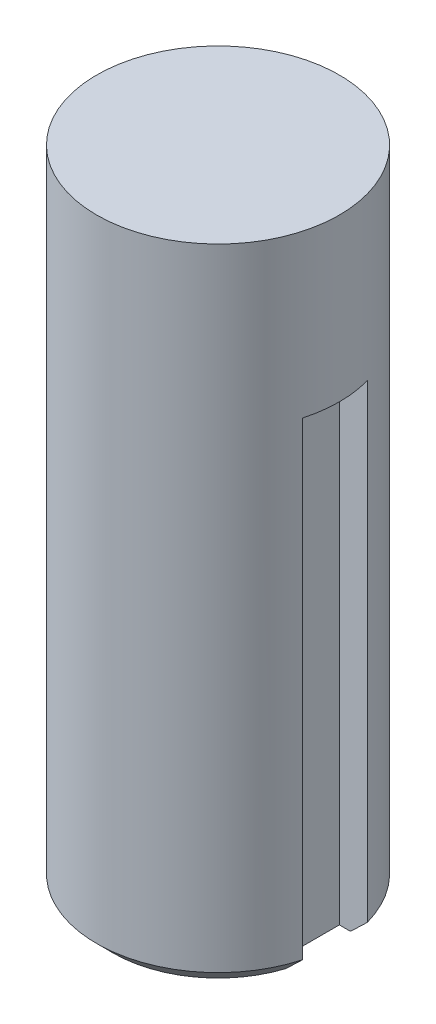
SolidWorks part; units mm, degrees
material "Malleable Cast Iron"
ref_plane "Front Plane" through (0, 0, 0) normal (0, 0, 1) x (1, 0, 0)
ref_plane "Top Plane" through (0, 0, 0) normal (0, 1, 0) x (1, 0, 0)
ref_plane "Right Plane" through (0, 0, 0) normal (1, 0, 0) x (0, 0, -1)
sketch "Sketch1" plane through (0, 0, 0) normal (0, 1, 0) x (1, 0, 0)
  line L0 (0, 0) -> (0, -50000) construction
  line L1 (0, 0) -> (-50000, 0) construction
  line L2 (11, 4) -> (11, -4)
  line L3 (11, 4) -> (14.4568, 4)
  line L4 (11, -4) -> (14.4568, -4)
  circle A0 centre (0, 0) radius 15
  point P10 (11, 0)
  dimension "D1" = 30
  dimension "D2" = 8
  dimension "D3" = 11
extrude "Boss-Extrude1" add sketch "Sketch1" along normal blind 80 contours L3 A0 L4 L2 | L4 A0 L3 L2 region at (12.9136, 0, 0) region at (-0.5836, 0, 0)
extrude "Cut-Extrude1" cut sketch "Sketch1<3>" along normal blind 60 contours L4 A0 L3 L2 region at (12.9136, 0, 0)
sketch "Sketch1<3>" plane through (0, 0, 0) normal (0, 1, 0) x (1, 0, 0) same geometry as "Sketch1"
fillet "Fillet1" radius 3 1 edges at (11, 60, 0) type face fillet first side face at (11, 30, 0) second side face at (12.8642, 60, 0)
chamfer "Chamfer1" distance 2 angle 45 1 edges at (-15, 0, 0)
